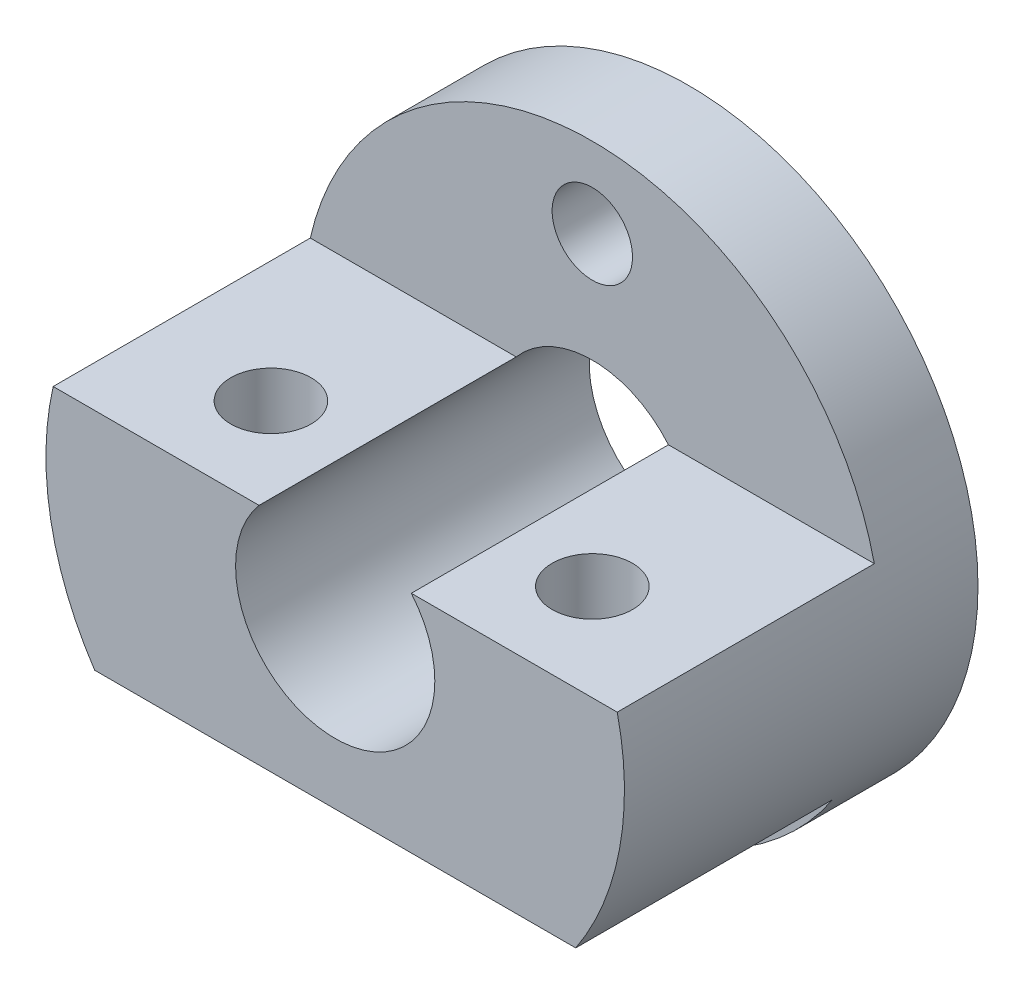
SolidWorks part; units mm, degrees
material "6061-T6 (SS)"
ref_plane "前视基准面" through (0, 0, 0) normal (0, 0, 1) x (1, 0, 0)
ref_plane "上视基准面" through (0, 0, 0) normal (0, 1, 0) x (1, 0, 0)
ref_plane "右视基准面" through (0, 0, 0) normal (1, 0, 0) x (0, 0, -1)
sketch "草图1" plane through (0, 0, 0) normal (0, 0, 1) x (1, 0, 0)
  circle A0 centre (0, 0) radius 9.5
  dimension "D1" = 19
extrude "凸台-拉伸1" add sketch "草图1" along normal blind 3
sketch "草图3" plane through (0, 0, 3) normal (0, 0, 1) x (1, 0, 0)
  circle A0 centre (0, 0) radius 9
  dimension "D1" = 18
extrude "凸台-拉伸2" add sketch "草图3" along normal blind 13
sketch "草图4" plane through (0, 0, 16) normal (0, 0, 1) x (1, 0, 0)
  line L0 (-8.775, 2) -> (8.775, 2)
  line L1 (-7.4833, -5) -> (7.4833, -5)
  circle A0 centre (0, 0) radius 9 construction
  circle A1 centre (0, 0) radius 9 construction
  arc A2 (-8.775, 2) -> (8.775, 2) centre (0, 0) cw
  arc A3 (7.4833, -5) -> (-7.4833, -5) centre (0, 0) cw
  dimension "D1" = 2
  dimension "D2" = 5
extrude "切除-拉伸2" cut sketch "草图4" against normal blind 13
sketch "草图5" plane through (0, 0, 16) normal (0, 0, 1) x (1, 0, 0)
  circle A0 centre (0, 0) radius 3.1
  dimension "D1" = 6.2
extrude "切除-拉伸3" cut sketch "草图5" against normal blind 20
sketch "草图6" plane through (0, 2, 0) normal (0, 1, 0) x (1, 0, 0)
  line L0 (2.3685, -3) -> (8.775, -3) construction
  line L1 (-8.775, -3) -> (-2.3685, -3) construction
  line L2 (-3.1, -16) -> (3.1, -16) construction
  circle A0 centre (-5, -8) radius 1.6
  circle A1 centre (5, -8) radius 1.6
  circle A2 centre (0, -14) radius 1.6
  dimension "D1" = 5
  dimension "D2" = 5
  dimension "D3" = 10
  dimension "D4" = 5
  dimension "D5" = 3.2
  dimension "D6" = 3.2
  dimension "D7" = 2
  dimension "D8" = 3.2
sketch "草图7" plane through (0, 0, 3) normal (0, 0, 1) x (1, 0, 0)
  line L0 (0, 0) -> (0, 6.5) construction
  line L1 (0, 0) -> (0, -6.5) construction
  circle A0 centre (0, 6.5) radius 1.3
  circle A1 centre (0, -6.5) radius 1.3
  dimension "D1" = 6.5
  dimension "D2" = 2.6
  dimension "D3" = 2.6
  dimension "D4" = 6.5
sketch "草图8" plane through (0, 0, 16) normal (0, 0, 1) x (1, 0, 0)
  circle A0 centre (0, 0) radius 9
extrude "切除-拉伸6" cut sketch "草图8" against normal blind 5
sketch "草图9" plane through (0, 0, 3) normal (0, 0, 1) x (1, 0, 0)
  circle A0 centre (0, 0) radius 9
extrude "切除-拉伸7" cut sketch "草图9" against normal blind 13 flip side to cut
hole_wizard "M3 螺纹孔1" positions "草图10" profile "草图11" tap size "M3" standard "GB" end condition through all
sketch "草图10" plane through (0, 2, 0) normal (0, 1, 0) x (1, 0, 0)
  point P0 (-5, -8)
  point P3 (5, -8)
sketch "草图11" plane through (-5, 2, 8) normal (1, 0, 0) x (0, 0, 1)
  line L0 (0, 0) -> (0, 11)
  line L1 (0, 11) -> (1.25, 11)
  line L2 (1.25, 11) -> (1.25, 0)
  line L5 (1.25, 0) -> (0, 0)
  line L11 (0, -6.35) -> (0, 107.95) construction
  dimension "通孔螺纹孔钻头直径" = 2.5
  dimension "通孔螺纹孔钻头深度" = 11
cosmetic thread "孔螺纹线1" parameters "D2"=3
cosmetic thread "孔螺纹线2" parameters "D2"=3
hole_wizard "M3 螺纹孔2" positions "草图12" profile "草图13" tap size "M3" standard "GB" end condition through all
sketch "草图12" plane through (0, 0, 3) normal (0, 0, 1) x (1, 0, 0)
  point P0 (0, 6.5)
  point P3 (0, -6.5)
sketch "草图13" plane through (0, 6.5, 3) normal (1, 0, 0) x (0, -1, 0)
  line L0 (0, 0) -> (0, 3)
  line L1 (0, 3) -> (1.25, 3)
  line L2 (1.25, 3) -> (1.25, 0)
  line L5 (1.25, 0) -> (0, 0)
  line L11 (0, -6.35) -> (0, 107.95) construction
  dimension "通孔螺纹孔钻头直径" = 2.5
  dimension "通孔螺纹孔钻头深度" = 3
cosmetic thread "孔螺纹线3" parameters "D2"=3
cosmetic thread "孔螺纹线4" parameters "D2"=3
